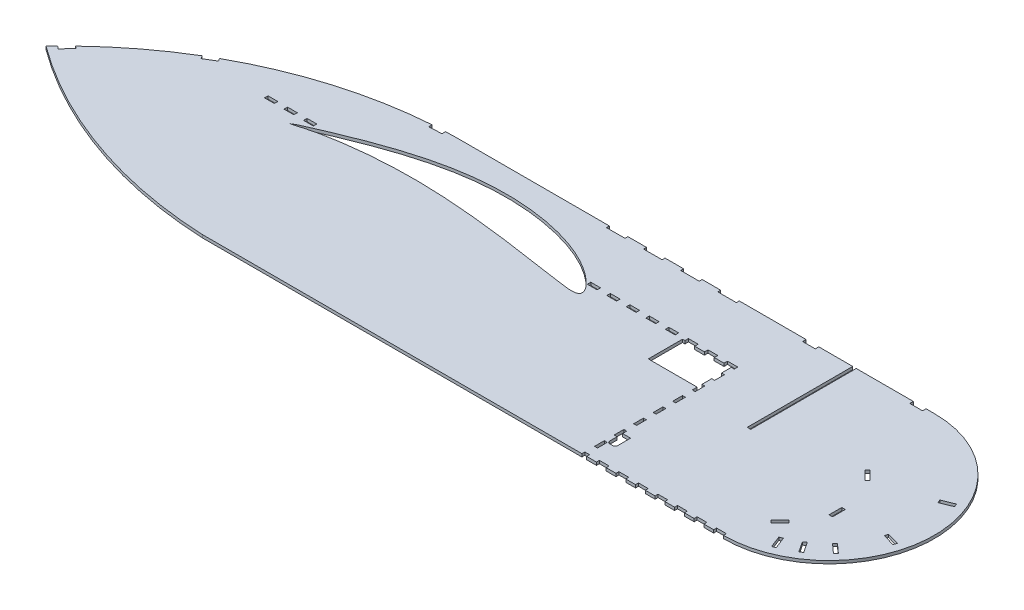
SolidWorks part; units mm, degrees
ref_plane "Front Plane" through (0, 0, 0) normal (0, 0, 1) x (1, 0, 0)
ref_plane "Top Plane" through (0, 0, 0) normal (0, 1, 0) x (1, 0, 0)
ref_plane "Right Plane" through (0, 0, 0) normal (1, 0, 0) x (0, 0, -1)
sketch "Sketch1" plane through (0, 0, 0) normal (0, 1, 0) x (1, 0, 0)
  line L0 (800, 108) -> (0, 108) construction
  line L1 (266.4083, 0) -> (800, 0)
  line L2 (0, 0) -> (0, 216) construction
  line L3 (316.2946, 216) -> (800, 216)
  arc A0 (800, 216) -> (800, 0) centre (800, 108) cw
  arc A2 (266.4083, 0) -> (19.4291, 86.8932) centre (286.1808, 450.645) cw
  arc A4 (19.4291, 86.8932) -> (316.2946, 216) centre (316.2946, -189.8565) cw
  dimension "D1" = 800
  dimension "D2" = 216
extrude "Boss-Extrude1" add sketch "Sketch1" along normal blind 3
sketch "Sketch2" plane through (0, 0, 0) normal (0, -1, 0) x (1, 0, 0)
  line L0 (605.07, -153) -> (605.07, 81) construction
  line L1 (647.57, -153) -> (637.57, -153)
  line L2 (655.07, -153) -> (655.07, -143)
  line L3 (655.07, -118) -> (605.07, -118)
  line L4 (823.6893, -121.2328) -> (814.4969, -130.4252)
  line L5 (814.4969, -130.4252) -> (817.0425, -132.9707)
  line L6 (817.0425, -132.9707) -> (826.2349, -123.7784)
  line L7 (826.2349, -123.7784) -> (823.6893, -121.2328)
  line L8 (823.6893, -121.2328) -> (814.4969, -130.4252)
  line L9 (814.4969, -130.4252) -> (817.0425, -132.9707)
  line L10 (817.0425, -132.9707) -> (826.2349, -123.7784)
  line L11 (826.2349, -123.7784) -> (823.6893, -121.2328)
  line L12 (605.07, -153) -> (605.07, -118)
  line L13 (778.5, -216) -> (791.5, -216) construction
  line L14 (791.5, -216) -> (791.5, -212.4) construction
  line L15 (791.5, -212.4) -> (778.5, -212.4) construction
  line L16 (778.5, -212.4) -> (778.5, -216) construction
  line L17 (668.6076, -216) -> (681.6076, -216) construction
  line L18 (681.6076, -216) -> (681.6076, -212.4) construction
  line L19 (681.6076, -212.4) -> (668.6076, -212.4) construction
  line L20 (833.2163, -28.1278) -> (837.9573, -16.0231)
  line L21 (837.9573, -16.0231) -> (834.6052, -14.7102)
  line L22 (834.6052, -14.7102) -> (829.8642, -26.8149)
  line L23 (829.8642, -26.8149) -> (833.2163, -28.1278)
  line L24 (833.2163, -28.1278) -> (837.9573, -16.0231)
  line L25 (837.9573, -16.0231) -> (834.6052, -14.7102)
  line L26 (834.6052, -14.7102) -> (829.8642, -26.8149)
  line L27 (829.8642, -26.8149) -> (833.2163, -28.1278)
  line L28 (839.4566, -85.3169) -> (839.4566, -72.3169)
  line L29 (839.4566, -72.3169) -> (835.8566, -72.3169)
  line L30 (835.8566, -72.3169) -> (835.8566, -85.3169)
  line L31 (835.8566, -85.3169) -> (839.4566, -85.3169)
  line L32 (839.4566, -85.3169) -> (839.4566, -72.3169)
  line L33 (839.4566, -72.3169) -> (835.8566, -72.3169)
  line L34 (835.8566, -72.3169) -> (835.8566, -85.3169)
  line L35 (835.8566, -85.3169) -> (839.4566, -85.3169)
  line L36 (668.6076, -212.4) -> (668.6076, -216) construction
  line L39 (600.2018, -213) -> (581.2018, -213) construction
  line L40 (658.07, -25.4734) -> (658.07, -38.6734)
  line L41 (663.77, -22.9734) -> (660.57, -22.9734)
  line L42 (666.27, -38.6734) -> (666.27, -25.4734)
  line L43 (658.07, -38.6734) -> (666.27, -38.6734)
  line L44 (658.07, -25.4734) -> (658.07, -33)
  line L45 (663.77, -22.9734) -> (660.57, -22.9734)
  line L46 (666.27, -38.6734) -> (666.27, -25.4734)
  line L47 (658.07, -38.6734) -> (666.27, -38.6734)
  line L48 (581.2018, -213) -> (581.2018, -216) construction
  line L49 (581.2018, -216) -> (600.2018, -216) construction
  line L50 (600.2018, -216) -> (600.2018, -213) construction
  line L51 (562.2018, -213) -> (543.2018, -213) construction
  line L52 (543.2018, -213) -> (543.2018, -216) construction
  line L53 (543.2018, -216) -> (562.2018, -216) construction
  line L54 (562.2018, -216) -> (562.2018, -213) construction
  line L55 (524.2018, -213) -> (505.2018, -213) construction
  line L56 (505.2018, -213) -> (505.2018, -216) construction
  line L57 (505.2018, -216) -> (524.2018, -216) construction
  line L58 (524.2018, -216) -> (524.2018, -213) construction
  line L59 (486.2018, -213) -> (467.2018, -213) construction
  line L60 (467.2018, -213) -> (467.2018, -216) construction
  line L61 (467.2018, -216) -> (486.2018, -216) construction
  line L62 (486.2018, -216) -> (486.2018, -213) construction
  line L63 (286.6536, -215.0679) -> (299.64, -215.6627) construction
  line L64 (299.64, -215.6627) -> (299.8047, -212.0664) construction
  line L65 (299.8047, -212.0664) -> (286.8183, -211.4717) construction
  line L66 (286.8183, -211.4717) -> (286.6536, -215.0679) construction
  line L67 (107.8918, -158.4076) -> (119.0512, -165.0761) construction
  line L68 (119.0512, -165.0761) -> (120.8979, -161.9858) construction
  line L69 (120.8979, -161.9858) -> (109.7385, -155.3173) construction
  line L70 (109.7385, -155.3173) -> (107.8918, -158.4076) construction
  line L71 (25.2251, -93.1105) -> (34.0897, -102.6194) construction
  line L72 (34.0897, -102.6194) -> (36.7229, -100.1646) construction
  line L73 (36.7229, -100.1646) -> (27.8584, -90.6557) construction
  line L74 (27.8584, -90.6557) -> (25.2251, -93.1105) construction
  line L79 (212.57, -142.8618) -> (212.57, -142.8948)
  line L131 (537.57, -153) -> (527.57, -153) construction
  line L132 (527.57, -153) -> (527.57, -156.6) construction
  line L133 (527.57, -156.6) -> (537.57, -156.6) construction
  line L134 (537.57, -156.6) -> (537.57, -153) construction
  line L135 (557.57, -153) -> (547.57, -153) construction
  line L136 (547.57, -153) -> (547.57, -156.6) construction
  line L137 (547.57, -156.6) -> (557.57, -156.6) construction
  line L138 (557.57, -156.6) -> (557.57, -153) construction
  line L139 (577.57, -153) -> (567.57, -153) construction
  line L140 (567.57, -153) -> (567.57, -156.6) construction
  line L141 (567.57, -156.6) -> (577.57, -156.6) construction
  line L142 (577.57, -156.6) -> (577.57, -153) construction
  line L143 (597.57, -153) -> (587.57, -153) construction
  line L144 (587.57, -153) -> (587.57, -156.6) construction
  line L145 (587.57, -156.6) -> (597.57, -156.6) construction
  line L146 (597.57, -156.6) -> (597.57, -153) construction
  line L148 (607.57, -153) -> (607.57, -156.6) construction
  line L149 (607.57, -156.6) -> (617.57, -156.6) construction
  line L150 (617.57, -156.6) -> (617.57, -153) construction
  line L152 (627.57, -153) -> (627.57, -156.6) construction
  line L153 (627.57, -156.6) -> (637.57, -156.6) construction
  line L154 (637.57, -156.6) -> (637.57, -153) construction
  line L155 (658.07, -153) -> (647.57, -153) construction
  line L156 (647.57, -153) -> (647.57, -156.6) construction
  line L157 (647.57, -156.6) -> (658.07, -156.6) construction
  line L158 (658.07, -156.6) -> (658.07, -153) construction
  line L160 (655.07, -143) -> (658.07, -143) construction
  line L161 (658.07, -143) -> (658.07, -133) construction
  line L162 (658.07, -133) -> (655.07, -133) construction
  line L163 (655.07, -113) -> (655.07, -123) construction
  line L164 (655.07, -123) -> (658.07, -123) construction
  line L165 (658.07, -123) -> (658.07, -113) construction
  line L166 (658.07, -113) -> (655.07, -113) construction
  line L167 (655.07, -93) -> (655.07, -103) construction
  line L168 (655.07, -103) -> (658.07, -103) construction
  line L169 (658.07, -103) -> (658.07, -93) construction
  line L170 (658.07, -93) -> (655.07, -93) construction
  line L171 (655.07, -73) -> (655.07, -83) construction
  line L172 (655.07, -83) -> (658.07, -83) construction
  line L173 (658.07, -83) -> (658.07, -73) construction
  line L174 (658.07, -73) -> (655.07, -73) construction
  line L175 (655.07, -53) -> (655.07, -63) construction
  line L176 (655.07, -63) -> (658.07, -63) construction
  line L177 (658.07, -63) -> (658.07, -53) construction
  line L178 (658.07, -53) -> (655.07, -53) construction
  line L179 (655.07, -33) -> (655.07, -43) construction
  line L180 (655.07, -43) -> (658.07, -43) construction
  line L182 (658.07, -33) -> (655.07, -33) construction
  line L183 (655.07, -13) -> (655.07, -23) construction
  line L184 (655.07, -23) -> (658.07, -23) construction
  line L185 (658.07, -23) -> (658.07, -13) construction
  line L186 (658.07, -13) -> (655.07, -13) construction
  line L187 (660, 0) -> (655.07, 0) construction
  line L188 (879.4661, -142.1765) -> (891.5128, -147.063) construction
  line L189 (891.5128, -147.063) -> (892.866, -143.727) construction
  line L190 (892.866, -143.727) -> (880.8193, -138.8405) construction
  line L191 (880.8193, -138.8405) -> (879.4661, -142.1765) construction
  line L192 (883.5641, -85.6407) -> (896.0497, -82.0199) construction
  line L193 (896.0497, -82.0199) -> (895.047, -78.5624) construction
  line L194 (895.047, -78.5624) -> (882.5614, -82.1832) construction
  line L195 (882.5614, -82.1832) -> (883.5641, -85.6407) construction
  line L196 (865.4007, -51.3816) -> (875.0501, -42.6702) construction
  line L197 (875.0501, -42.6702) -> (872.6378, -39.9981) construction
  line L198 (872.6378, -39.9981) -> (862.9883, -48.7095) construction
  line L199 (862.9883, -48.7095) -> (865.4007, -51.3816) construction
  line L200 (849.1147, -36.7915) -> (856.2715, -25.9389) construction
  line L201 (856.2715, -25.9389) -> (853.2661, -23.957) construction
  line L202 (853.2661, -23.957) -> (846.1093, -34.8096) construction
  line L203 (846.1093, -34.8096) -> (849.1147, -36.7915) construction
  line L204 (822.4089, -44.7346) -> (813.2165, -35.5422) construction
  line L205 (813.2165, -35.5422) -> (810.6709, -38.0878) construction
  line L206 (810.6709, -38.0878) -> (819.8633, -47.2801) construction
  line L207 (819.8633, -47.2801) -> (822.4089, -44.7346) construction
  line L208 (879.4661, -142.1765) -> (891.5128, -147.063)
  line L209 (891.5128, -147.063) -> (892.866, -143.727)
  line L210 (892.866, -143.727) -> (880.8193, -138.8405)
  line L211 (880.8193, -138.8405) -> (879.4661, -142.1765)
  line L212 (883.5641, -85.6407) -> (896.0497, -82.0199)
  line L213 (896.0497, -82.0199) -> (895.047, -78.5624)
  line L214 (895.047, -78.5624) -> (882.5614, -82.1832)
  line L215 (882.5614, -82.1832) -> (883.5641, -85.6407)
  line L216 (865.4007, -51.3816) -> (875.0501, -42.6702)
  line L217 (875.0501, -42.6702) -> (872.6378, -39.9981)
  line L218 (872.6378, -39.9981) -> (862.9883, -48.7095)
  line L219 (862.9883, -48.7095) -> (865.4007, -51.3816)
  line L220 (849.1147, -36.7915) -> (856.2715, -25.9389)
  line L221 (856.2715, -25.9389) -> (853.2661, -23.957)
  line L222 (853.2661, -23.957) -> (846.1093, -34.8096)
  line L223 (846.1093, -34.8096) -> (849.1147, -36.7915)
  line L224 (822.4089, -44.7346) -> (813.2165, -35.5422)
  line L225 (813.2165, -35.5422) -> (810.6709, -38.0878)
  line L226 (810.6709, -38.0878) -> (819.8633, -47.2801)
  line L227 (819.8633, -47.2801) -> (822.4089, -44.7346)
  line L228 (655.07, 0) -> (655.07, -3) construction
  line L229 (655.07, -3) -> (660, -3) construction
  line L230 (660, -3) -> (660, 0) construction
  line L231 (680, 0) -> (670, 0) construction
  line L232 (670, 0) -> (670, -3) construction
  line L233 (670, -3) -> (680, -3) construction
  line L234 (680, -3) -> (680, 0) construction
  line L235 (700, 0) -> (690, 0) construction
  line L236 (690, 0) -> (690, -3) construction
  line L237 (690, -3) -> (700, -3) construction
  line L238 (700, -3) -> (700, 0) construction
  line L239 (720, 0) -> (710, 0) construction
  line L240 (710, 0) -> (710, -3) construction
  line L241 (710, -3) -> (720, -3) construction
  line L242 (720, -3) -> (720, 0) construction
  line L243 (740, 0) -> (730, 0) construction
  line L244 (730, 0) -> (730, -3) construction
  line L245 (730, -3) -> (740, -3) construction
  line L246 (740, -3) -> (740, 0) construction
  line L247 (760, 0) -> (750, 0) construction
  line L248 (750, 0) -> (750, -3) construction
  line L249 (750, -3) -> (760, -3) construction
  line L250 (760, -3) -> (760, 0) construction
  line L251 (780, 0) -> (770, 0) construction
  line L252 (770, 0) -> (770, -3) construction
  line L253 (770, -3) -> (780, -3) construction
  line L254 (780, -3) -> (780, 0) construction
  line L255 (800, 0) -> (790, 0) construction
  line L256 (790, 0) -> (790, -3) construction
  line L257 (790, -3) -> (800, -3) construction
  line L258 (800, -3) -> (800, 0) construction
  line L259 (778.5, -216) -> (791.5, -216)
  line L260 (791.5, -216) -> (791.5, -212.4)
  line L261 (791.5, -212.4) -> (778.5, -212.4)
  line L262 (778.5, -212.4) -> (778.5, -216)
  line L263 (668.6076, -216) -> (681.6076, -216)
  line L264 (681.6076, -216) -> (681.6076, -212.4)
  line L265 (681.6076, -212.4) -> (668.6076, -212.4)
  line L266 (668.6076, -212.4) -> (668.6076, -216)
  line L267 (600.2018, -213) -> (581.2018, -213)
  line L268 (581.2018, -213) -> (581.2018, -216)
  line L269 (581.2018, -216) -> (600.2018, -216)
  line L270 (600.2018, -216) -> (600.2018, -213)
  line L271 (562.2018, -213) -> (543.2018, -213)
  line L272 (543.2018, -213) -> (543.2018, -216)
  line L273 (543.2018, -216) -> (562.2018, -216)
  line L274 (562.2018, -216) -> (562.2018, -213)
  line L275 (524.2018, -213) -> (505.2018, -213)
  line L276 (505.2018, -213) -> (505.2018, -216)
  line L277 (505.2018, -216) -> (524.2018, -216)
  line L278 (524.2018, -216) -> (524.2018, -213)
  line L279 (486.2018, -213) -> (467.2018, -213)
  line L280 (467.2018, -213) -> (467.2018, -216)
  line L281 (467.2018, -216) -> (486.2018, -216)
  line L282 (486.2018, -216) -> (486.2018, -213)
  line L283 (286.6536, -215.0679) -> (299.64, -215.6627)
  line L284 (299.64, -215.6627) -> (299.8047, -212.0664)
  line L285 (299.8047, -212.0664) -> (286.8183, -211.4717)
  line L286 (286.8183, -211.4717) -> (286.6536, -215.0679)
  line L287 (107.8918, -158.4076) -> (119.0512, -165.0761)
  line L288 (119.0512, -165.0761) -> (120.8979, -161.9858)
  line L289 (120.8979, -161.9858) -> (109.7385, -155.3173)
  line L290 (109.7385, -155.3173) -> (107.8918, -158.4076)
  line L291 (25.2251, -93.1105) -> (34.0897, -102.6194)
  line L292 (34.0897, -102.6194) -> (36.7229, -100.1646)
  line L293 (36.7229, -100.1646) -> (27.8584, -90.6557)
  line L294 (27.8584, -90.6557) -> (25.2251, -93.1105)
  line L351 (537.57, -153) -> (527.57, -153)
  line L352 (527.57, -153) -> (527.57, -156.6)
  line L353 (527.57, -156.6) -> (537.57, -156.6)
  line L354 (537.57, -156.6) -> (537.57, -153)
  line L355 (557.57, -153) -> (547.57, -153)
  line L356 (547.57, -153) -> (547.57, -156.6)
  line L357 (547.57, -156.6) -> (557.57, -156.6)
  line L358 (557.57, -156.6) -> (557.57, -153)
  line L359 (577.57, -153) -> (567.57, -153)
  line L360 (567.57, -153) -> (567.57, -156.6)
  line L361 (567.57, -156.6) -> (577.57, -156.6)
  line L362 (577.57, -156.6) -> (577.57, -153)
  line L363 (597.57, -153) -> (587.57, -153)
  line L364 (587.57, -153) -> (587.57, -156.6)
  line L365 (587.57, -156.6) -> (597.57, -156.6)
  line L366 (597.57, -156.6) -> (597.57, -153)
  line L368 (607.57, -153) -> (607.57, -156.6)
  line L369 (607.57, -156.6) -> (617.57, -156.6)
  line L370 (617.57, -156.6) -> (617.57, -153)
  line L372 (627.57, -153) -> (627.57, -156.6)
  line L373 (627.57, -156.6) -> (637.57, -156.6)
  line L374 (637.57, -156.6) -> (637.57, -153)
  line L375 (658.07, -153) -> (655.07, -153)
  line L376 (647.57, -153) -> (647.57, -156.6)
  line L377 (647.57, -156.6) -> (658.07, -156.6)
  line L378 (658.07, -156.6) -> (658.07, -153)
  line L380 (655.07, -143) -> (658.07, -143)
  line L381 (658.07, -143) -> (658.07, -133)
  line L382 (658.07, -133) -> (655.07, -133)
  line L383 (655.07, -113) -> (655.07, -118)
  line L384 (655.07, -123) -> (658.07, -123)
  line L385 (658.07, -123) -> (658.07, -113)
  line L386 (658.07, -113) -> (655.07, -113)
  line L387 (655.07, -93) -> (655.07, -103)
  line L388 (655.07, -103) -> (658.07, -103)
  line L389 (658.07, -103) -> (658.07, -93)
  line L390 (658.07, -93) -> (655.07, -93)
  line L391 (655.07, -73) -> (655.07, -83)
  line L392 (655.07, -83) -> (658.07, -83)
  line L393 (658.07, -83) -> (658.07, -73)
  line L394 (658.07, -73) -> (655.07, -73)
  line L395 (655.07, -53) -> (655.07, -63)
  line L396 (655.07, -63) -> (658.07, -63)
  line L397 (658.07, -63) -> (658.07, -53)
  line L398 (658.07, -53) -> (655.07, -53)
  line L399 (655.07, -33) -> (655.07, -43)
  line L400 (655.07, -43) -> (658.07, -43)
  line L401 (658.07, -43) -> (658.07, -38.6734)
  line L402 (658.07, -33) -> (655.07, -33)
  line L403 (655.07, -13) -> (655.07, -23)
  line L404 (655.07, -23) -> (658.07, -23)
  line L405 (658.07, -23) -> (658.07, -13)
  line L406 (658.07, -13) -> (655.07, -13)
  line L407 (660, 0) -> (655.07, 0)
  line L408 (655.07, 0) -> (655.07, -3)
  line L409 (655.07, -3) -> (660, -3)
  line L410 (660, -3) -> (660, 0)
  line L411 (680, 0) -> (670, 0)
  line L412 (670, 0) -> (670, -3)
  line L413 (670, -3) -> (680, -3)
  line L414 (680, -3) -> (680, 0)
  line L415 (700, 0) -> (690, 0)
  line L416 (690, 0) -> (690, -3)
  line L417 (690, -3) -> (700, -3)
  line L418 (700, -3) -> (700, 0)
  line L419 (720, 0) -> (710, 0)
  line L420 (710, 0) -> (710, -3)
  line L421 (710, -3) -> (720, -3)
  line L422 (720, -3) -> (720, 0)
  line L423 (740, 0) -> (730, 0)
  line L424 (730, 0) -> (730, -3)
  line L425 (730, -3) -> (740, -3)
  line L426 (740, -3) -> (740, 0)
  line L427 (760, 0) -> (750, 0)
  line L428 (750, 0) -> (750, -3)
  line L429 (750, -3) -> (760, -3)
  line L430 (760, -3) -> (760, 0)
  line L431 (780, 0) -> (770, 0)
  line L432 (770, 0) -> (770, -3)
  line L433 (770, -3) -> (780, -3)
  line L434 (780, -3) -> (780, 0)
  line L435 (800, 0) -> (790, 0)
  line L436 (790, 0) -> (790, -3)
  line L437 (790, -3) -> (800, -3)
  line L438 (800, -3) -> (800, 0)
  line L439 (655.07, -133) -> (655.07, -123)
  line L440 (627.57, -153) -> (617.57, -153)
  line L441 (607.57, -153) -> (605.07, -153)
  line L462 (187.07, -153) -> (177.07, -153) construction
  line L463 (177.07, -153) -> (177.07, -156.6) construction
  line L464 (177.07, -156.6) -> (187.07, -156.6) construction
  line L465 (187.07, -156.6) -> (187.07, -153) construction
  line L466 (207.07, -153) -> (197.07, -153) construction
  line L467 (197.07, -153) -> (197.07, -156.6) construction
  line L468 (197.07, -156.6) -> (207.07, -156.6) construction
  line L469 (207.07, -156.6) -> (207.07, -153) construction
  line L470 (227.07, -153) -> (217.07, -153) construction
  line L471 (217.07, -153) -> (217.07, -156.6) construction
  line L472 (217.07, -156.6) -> (227.07, -156.6) construction
  line L473 (227.07, -156.6) -> (227.07, -153) construction
  line L474 (517.57, -153) -> (507.57, -153) construction
  line L475 (507.57, -153) -> (507.57, -156.6) construction
  line L476 (507.57, -156.6) -> (517.57, -156.6) construction
  line L477 (517.57, -156.6) -> (517.57, -153) construction
  line L478 (187.07, -153) -> (177.07, -153)
  line L479 (177.07, -153) -> (177.07, -156.6)
  line L480 (177.07, -156.6) -> (187.07, -156.6)
  line L481 (187.07, -156.6) -> (187.07, -153)
  line L482 (207.07, -153) -> (197.07, -153)
  line L483 (197.07, -153) -> (197.07, -156.6)
  line L484 (197.07, -156.6) -> (207.07, -156.6)
  line L485 (207.07, -156.6) -> (207.07, -153)
  line L486 (227.07, -153) -> (217.07, -153)
  line L487 (217.07, -153) -> (217.07, -156.6)
  line L488 (217.07, -156.6) -> (227.07, -156.6)
  line L489 (227.07, -156.6) -> (227.07, -153)
  line L490 (517.57, -153) -> (507.57, -153)
  line L491 (507.57, -153) -> (507.57, -156.6)
  line L492 (507.57, -156.6) -> (517.57, -156.6)
  line L493 (517.57, -156.6) -> (517.57, -153)
  line L534 (716.4, -108) -> (716.4, -216)
  line L535 (716.4, -216) -> (720, -216)
  line L536 (720, -216) -> (720, -108)
  line L537 (720, -108) -> (716.4, -108)
  line L538 (716.4, -108) -> (716.4, -216)
  line L539 (716.4, -216) -> (720, -216)
  line L540 (720, -216) -> (720, -108)
  line L541 (720, -108) -> (716.4, -108)
  arc A2 (660.57, -22.9734) -> (658.07, -25.4734) centre (660.57, -25.4734) ccw
  arc A3 (666.27, -25.4734) -> (663.77, -22.9734) centre (663.77, -25.4734) ccw
  arc A4 (660.57, -22.9734) -> (658.07, -25.4734) centre (660.57, -25.4734) ccw
  arc A5 (666.27, -25.4734) -> (663.77, -22.9734) centre (663.77, -25.4734) ccw
  spline S1 degree 3 poles (-377.7086, -949.9382) (192.79, -109.3212) (198.5516, -134.6969) (215.6642, -144.8206) (218.7234, -146.3779) (222.7838, -148.1804) (227.7591, -150.3808) (233.6732, -152.9729) (243.3346, -157.074) (254.0716, -161.5286) (265.8113, -166.1514) (275.5598, -169.7926) (285.8203, -173.3897) (300.2132, -178.0429) (315.0475, -182.2144) (330.2168, -185.6782) (341.7168, -187.8628) (353.2384, -189.5705) (364.7498, -190.7898) (376.2222, -191.4893) (387.6115, -191.6869) (398.8538, -191.3647) (413.4214, -190.2963) (427.5808, -188.3) (441.1954, -185.4275) (450.8219, -182.9197) (459.9489, -180.0697) (468.5117, -176.8876) (476.4536, -173.4247) (483.7151, -169.7289) (490.2481, -165.8848) (496.0197, -162.0069) (500.998, -158.1857) (505.1476, -154.4841) (508.4473, -150.9827) (510.8522, -147.7808) (512.2305, -145.119) (512.6724, -143.038) (512.366, -141.294) (510.8363, -139.8679) (508.3008, -139.2046) (504.9907, -138.9969) (500.8451, -139.2329) (495.8864, -139.807) (490.1274, -140.6338) (483.6007, -141.6142) (476.346, -142.682) (468.4189, -143.8709) (459.8696, -145.153) (447.4042, -147.014) (434.3028, -148.892) (413.2306, -151.6803) (394.9165, -153.7705) (372.4131, -155.7852) (353.2786, -157.0974) (334.1039, -157.7205) (318.8375, -157.7193) (307.5693, -157.4631) (296.5448, -156.9424) (285.8536, -156.1986) (275.5863, -155.2546) (265.8296, -154.1569) (256.6735, -152.9128) (248.205, -151.5585) (240.5101, -150.1233) (233.6661, -148.6641) (227.7356, -147.2296) (222.7715, -145.8056) (218.7746, -144.5126) (215.7248, -143.5952) (197.5782, -139.0065) (176.9662, -151.1292) (372.0571, 844.103) knots -0.084186 -0.084186 -0.084186 -0.084186 0.001413 0.005226 0.010781 0.017816 0.026461 0.036791 0.048686 0.076639 0.092363 0.109003 0.126387 0.144339 0.181313 0.200023 0.218713 0.237261 0.255692 0.274037 0.292193 0.310133 0.327788 0.362002 0.378421 0.394287 0.409543 0.424114 0.437938 0.450942 0.463044 0.474154 0.484165 0.493024 0.500713 0.507126 0.51213 0.514904 0.517171 0.520262 0.524245 0.529498 0.536092 0.544061 0.553363 0.563905 0.575615 0.58842 0.602227 0.616944 0.648676 0.665501 0.718564 0.736789 0.773513 0.810245 0.828489 0.846493 0.864125 0.881249 0.897725 0.913415 0.928184 0.941897 0.954411 0.965603 0.97535 0.983576 0.990285 0.995433 0.9988 1.079713 1.079713 1.079713 1.079713 only from (212.57, -142.8948) to (212.57, -142.8618) construction
  spline S2 degree 3 poles (212.57, -142.8948) (212.8151, -143.0601) (213.7215, -143.6713) (215.6642, -144.8206) (218.7234, -146.3779) (222.7838, -148.1804) (227.7591, -150.3808) (233.6732, -152.9729) (243.3346, -157.074) (254.0716, -161.5286) (265.8113, -166.1514) (275.5598, -169.7926) (285.8203, -173.3897) (300.2132, -178.0429) (315.0475, -182.2144) (330.2168, -185.6782) (341.7168, -187.8628) (353.2384, -189.5705) (364.7498, -190.7898) (376.2222, -191.4893) (387.6115, -191.6869) (398.8538, -191.3647) (413.4214, -190.2963) (427.5808, -188.3) (441.1954, -185.4275) (450.8219, -182.9197) (459.9489, -180.0697) (468.5117, -176.8876) (476.4536, -173.4247) (483.7151, -169.7289) (490.2481, -165.8848) (496.0197, -162.0069) (500.998, -158.1857) (505.1476, -154.4841) (508.4473, -150.9827) (510.8522, -147.7808) (512.2305, -145.119) (512.6724, -143.038) (512.366, -141.294) (510.8363, -139.8679) (508.3008, -139.2046) (504.9907, -138.9969) (500.8451, -139.2329) (495.8864, -139.807) (490.1274, -140.6338) (483.6007, -141.6142) (476.346, -142.682) (468.4189, -143.8709) (459.8696, -145.153) (447.4042, -147.014) (434.3028, -148.892) (413.2306, -151.6803) (394.9165, -153.7705) (372.4131, -155.7852) (353.2786, -157.0974) (334.1039, -157.7205) (318.8375, -157.7193) (307.5693, -157.4631) (296.5448, -156.9424) (285.8536, -156.1986) (275.5863, -155.2546) (265.8296, -154.1569) (256.6735, -152.9128) (248.205, -151.5585) (240.5101, -150.1233) (233.6661, -148.6641) (227.7356, -147.2296) (222.7715, -145.8056) (218.7746, -144.5126) (215.7248, -143.5952) (213.7534, -143.0967) (212.8162, -142.9107) (212.57, -142.8618) knots 0 0 0 0 0.001413 0.005226 0.010781 0.017816 0.026461 0.036791 0.048686 0.076639 0.092363 0.109003 0.126387 0.144339 0.181313 0.200023 0.218713 0.237261 0.255692 0.274037 0.292193 0.310133 0.327788 0.362002 0.378421 0.394287 0.409543 0.424114 0.437938 0.450942 0.463044 0.474154 0.484165 0.493024 0.500713 0.507126 0.51213 0.514904 0.517171 0.520262 0.524245 0.529498 0.536092 0.544061 0.553363 0.563905 0.575615 0.58842 0.602227 0.616944 0.648676 0.665501 0.718564 0.736789 0.773513 0.810245 0.828489 0.846493 0.864125 0.881249 0.897725 0.913415 0.928184 0.941897 0.954411 0.965603 0.97535 0.983576 0.990285 0.995433 0.9988 1 1 1 1
  dimension "D6" = 35
  dimension "D1" = 0
  dimension "D2" = 0
  dimension "D3" = 0
  dimension "D4" = 0
  dimension "D5" = 0
extrude "Cut-Extrude1" cut sketch "Sketch2" against normal through all
